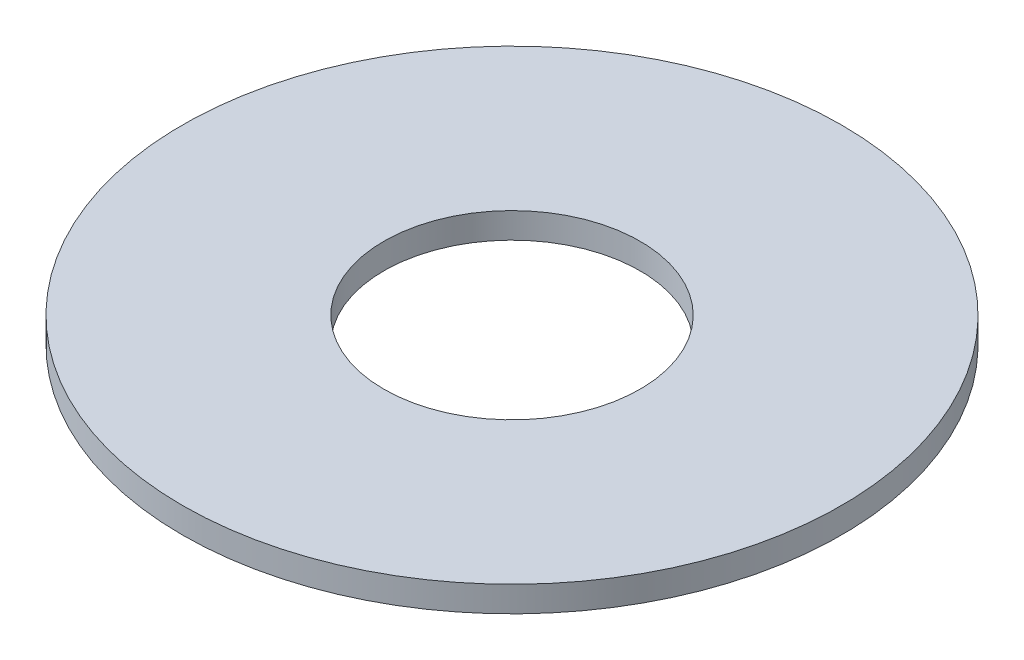
SolidWorks part; units mm, degrees
ref_plane "Front Plane" through (0, 0, 0) normal (0, 0, 1) x (1, 0, 0)
ref_plane "Top Plane" through (0, 0, 0) normal (0, 1, 0) x (1, 0, 0)
ref_plane "Right Plane" through (0, 0, 0) normal (1, 0, 0) x (0, 0, -1)
sketch "Sketch1" plane through (0, 0, 0) normal (0, 1, 0) x (1, 0, 0)
  circle A0 centre (0, 0) radius 90
  dimension "FLANGE_OD" = 180
extrude "Boss-Extrude1" add sketch "Sketch1" along normal blind 7
sketch "Sketch2" plane through (0, 0, 0) normal (0, 1, 0) x (1, 0, 0)
  circle A0 centre (0, 0) radius 35
  dimension "BORE_D" = 70
extrude "Cut-Extrude1" cut sketch "Sketch2" along normal through all
sketch "Sketch3" plane through (0, 7, 0) normal (0, 1, 0) x (1, 0, 0)
  circle A0 centre (0, 0) radius 27.3836 construction
  circle A1 centre (-27.3836, 0) radius 5.9904
  dimension "BOLT_D" = 11.9809
  dimension "BOLT_PCD" = 54.7671
extrude "Cut-Extrude2" cut sketch "Sketch3" against normal blind 4.989 rebuild error yes
pattern_circular "CirPattern1" count 5 over 360 rebuild error yes
